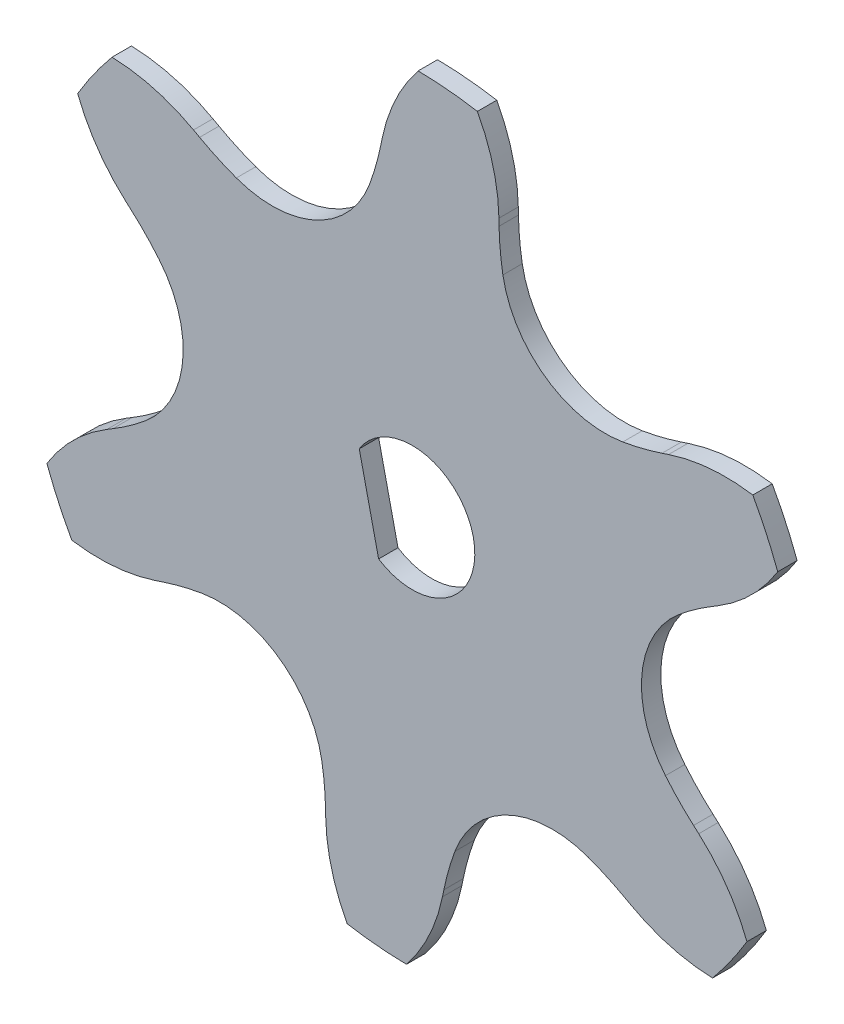
SolidWorks part; units mm, degrees
ref_plane "Front Plane" through (0, 0, 0) normal (0, 0, 1) x (1, 0, 0)
ref_plane "Top Plane" through (0, 0, 0) normal (0, 1, 0) x (1, 0, 0)
ref_plane "Right Plane" through (0, 0, 0) normal (1, 0, 0) x (0, 0, -1)
sketch "Sketch1" plane through (0, 0, 0) normal (0, 0, 1) x (1, 0, 0)
  circle A0 centre (0, 0) radius 34.8677
base flange "Base-Flange1" sketch "Sketch1" thickness 0.7366 reverse thickness direction no parameters "D1"=0.7366
extrude "Cut-Extrude1" cut sketch "Sketch2" against normal through all both and the other way through all normal cut yes
sketch "Sketch2" plane through (-59.5553, -54.6189, 100.9067) normal (0, 0, -1) x (-1, 0, 0)
  line L7 (-81.3444, 48.0853) -> (-81.1474, 48.2601)
  line L8 (-78.5436, 44.5741) -> (-78.7742, 44.4468)
  line L11 (-67.1679, 41.8115) -> (-67.1729, 41.5482)
  line L12 (-71.609, 41.1416) -> (-71.6619, 41.3996)
  line L13 (-80.1987, 59.9882) -> (-79.9488, 59.905)
  line L14 (-81.8391, 55.8071) -> (-82.0646, 55.9431)
  line L15 (-69.3176, 64.9475) -> (-69.2648, 64.6894)
  line L16 (-73.7587, 64.2775) -> (-73.7537, 64.5409)
  line L17 (-59.5822, 58.0038) -> (-59.7793, 57.829)
  line L18 (-62.383, 61.515) -> (-62.1524, 61.6423)
  line L19 (-60.7279, 46.1008) -> (-60.9778, 46.1841)
  line L20 (-59.0875, 50.282) -> (-58.862, 50.1459)
  arc A29 (-80.0788, 49.3629) -> (-80.5878, 54.9169) centre (-83.1103, 51.8854) ccw
  arc A30 (-81.1474, 48.2601) -> (-80.0788, 49.3629) centre (-87.89, 55.8625) ccw
  arc A31 (-81.3444, 48.0853) -> (-83.1754, 45.4488) centre (-76.8322, 42.9978) ccw
  arc A32 (-83.1754, 45.4488) -> (-81.8711, 43.6024) centre (-70.4633, 53.0445) ccw
  arc A33 (-81.8711, 43.6024) -> (-78.7742, 44.4468) centre (-82.061, 50.4) ccw
  arc A34 (-77.1471, 45.2126) -> (-78.5436, 44.5741) centre (-73.6322, 35.6782) ccw
  arc A41 (-67.0226, 43.3403) -> (-67.1679, 41.8115) centre (-57.0081, 41.6171) ccw
  arc A42 (-67.9901, 38.444) -> (-67.1729, 41.5482) centre (-73.9719, 41.6783) ccw
  arc A43 (-70.2412, 38.2377) -> (-67.9901, 38.444) centre (-70.4633, 53.0445) ccw
  arc A44 (-71.609, 41.1416) -> (-70.2412, 38.2377) centre (-64.947, 42.5055) ccw
  arc A45 (-71.6619, 41.3996) -> (-72.0827, 42.8765) centre (-81.617, 39.3616) ccw
  arc A46 (-72.0827, 42.8765) -> (-77.1471, 45.2126) centre (-75.7829, 41.5123) ccw
  arc A47 (-78.4594, 59.531) -> (-73.9041, 62.7488) centre (-77.7907, 63.4176) ccw
  arc A48 (-79.9488, 59.905) -> (-78.4594, 59.531) centre (-76.7363, 69.5454) ccw
  arc A49 (-80.1987, 59.9882) -> (-83.3975, 60.2556) centre (-82.3485, 53.5368) ccw
  arc A50 (-83.3975, 60.2556) -> (-84.3444, 58.2029) centre (-70.4633, 53.0445) ccw
  arc A51 (-84.3444, 58.2029) -> (-82.0646, 55.9431) centre (-78.5524, 61.7662) ccw
  arc A52 (-80.5878, 54.9169) -> (-81.8391, 55.8071) centre (-87.0874, 47.1057) ccw
  arc A53 (-68.844, 63.2126) -> (-63.7795, 60.8764) centre (-65.1437, 64.5767) ccw
  arc A54 (-69.2648, 64.6894) -> (-68.844, 63.2126) centre (-59.3096, 66.7275) ccw
  arc A55 (-69.3176, 64.9475) -> (-70.6854, 67.8514) centre (-75.9796, 63.5836) ccw
  arc A56 (-70.6854, 67.8514) -> (-72.9365, 67.6451) centre (-70.4633, 53.0445) ccw
  arc A57 (-72.9365, 67.6451) -> (-73.7537, 64.5409) centre (-66.9547, 64.4107) ccw
  arc A58 (-73.9041, 62.7488) -> (-73.7587, 64.2775) centre (-83.9185, 64.472) ccw
  arc A59 (-60.8479, 56.7262) -> (-60.3388, 51.1722) centre (-57.8163, 54.2037) ccw
  arc A60 (-59.7793, 57.829) -> (-60.8479, 56.7262) centre (-53.0366, 50.2266) ccw
  arc A61 (-59.5822, 58.0038) -> (-57.7513, 60.6403) centre (-64.0944, 63.0913) ccw
  arc A62 (-57.7513, 60.6403) -> (-59.0555, 62.4867) centre (-70.4633, 53.0445) ccw
  arc A63 (-59.0555, 62.4867) -> (-62.1524, 61.6423) centre (-58.8656, 55.6891) ccw
  arc A64 (-63.7795, 60.8764) -> (-62.383, 61.515) centre (-67.2945, 70.4108) ccw
  arc A65 (-62.4672, 46.5581) -> (-67.0226, 43.3403) centre (-63.136, 42.6715) ccw
  arc A66 (-60.9778, 46.1841) -> (-62.4672, 46.5581) centre (-64.1904, 36.5436) ccw
  arc A67 (-60.7279, 46.1008) -> (-57.5292, 45.8334) centre (-58.5781, 52.5523) ccw
  arc A68 (-57.5292, 45.8334) -> (-56.5823, 47.8862) centre (-70.4633, 53.0445) ccw
  arc A69 (-56.5823, 47.8862) -> (-58.862, 50.1459) centre (-62.3742, 44.3229) ccw
  arc A70 (-60.3388, 51.1722) -> (-59.0875, 50.282) centre (-53.8392, 58.9834) ccw
  circle A71 centre (-70.4633, 53.0445) radius 180.5532
  point P87 (-70.4633, 53.0445)
extrude "Cut-Extrude2" cut sketch "Sketch3" against normal through all both and the other way through all normal cut yes
sketch "Sketch3" plane through (-59.5553, -54.6189, 92.5632) normal (0, 0, -1) x (-1, 0, 0)
  line L0 (-69.1834, 51.044) -> (-68.448, 54.301)
  arc A0 (-69.1834, 51.044) -> (-68.448, 54.301) centre (-70.4633, 53.0445) cw
sketch "Bend-Lines1" plane through (0, 0, 0) normal (0, 1, 0) x (1, 0, 0)
sketch "Bounding-Box1" plane through (0, 0, 0) normal (0, 1, 0) x (1, 0, 0)
sheet metal parameters "Sheet-Metal1" thickness 0.7366 parameters "D1"=0.7366
flat pattern "Flat-Pattern1" [suppressed]
sketch "Bend-Lines2" plane through (0, 0, 0) normal (0, 1, 0) x (1, 0, 0)
sketch "Bounding-Box2" [suppressed] plane through (0, 0, 0) normal (0, 1, 0) x (1, 0, 0)
sheet metal parameters "Sheet-Metal2" thickness 0.7366 parameters "D1"=0.7366
flat pattern "Flat-Pattern1"
sketch "Bend-Lines2" plane through (0, 0, 0) normal (0, 1, 0) x (1, 0, 0)
sketch "Bounding-Box2" [suppressed] plane through (0, 0, 0) normal (0, 1, 0) x (1, 0, 0)
sheet metal parameters "Sheet-Metal3" thickness 0.7366 parameters "D1"=0.7366
flat pattern "Flat-Pattern1"
sketch "Bend-Lines2" plane through (0, 0, 0) normal (0, 1, 0) x (1, 0, 0)
sketch "Bounding-Box2" [suppressed] plane through (0, 0, 0) normal (0, 1, 0) x (1, 0, 0)
